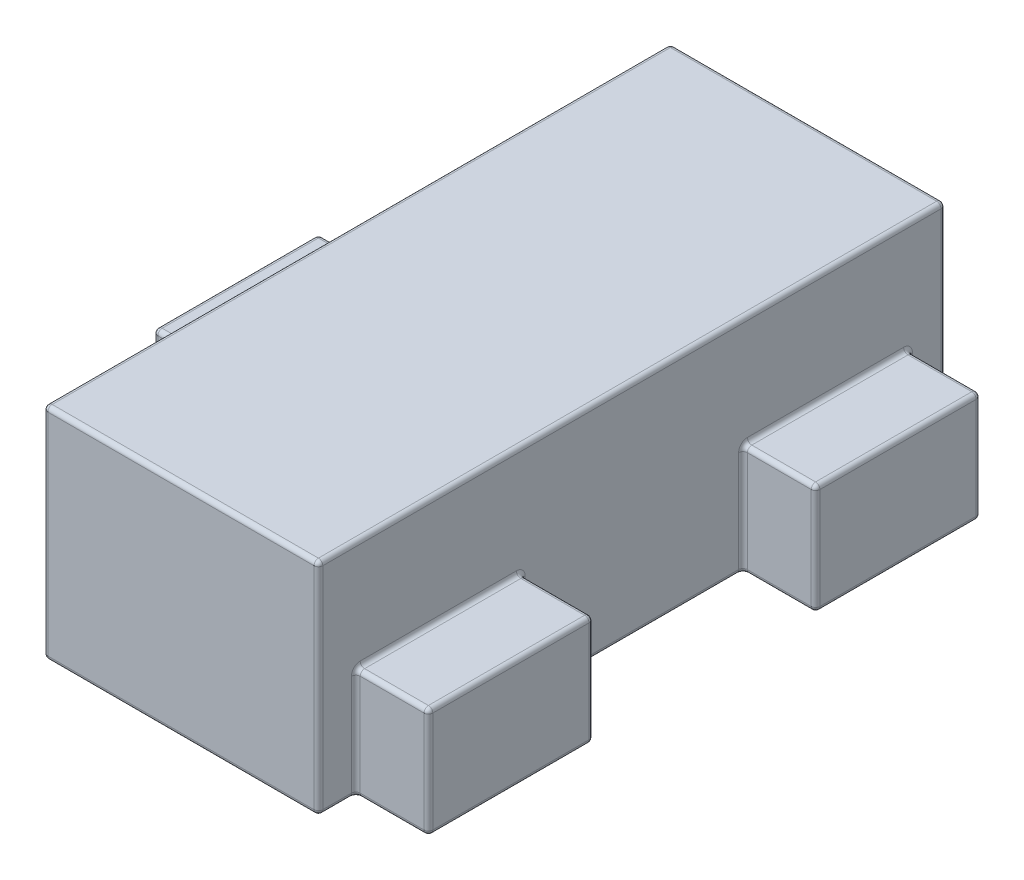
SolidWorks part; units mm, degrees
ref_plane "Front Plane" through (0, 0, 0) normal (0, 0, 1) x (1, 0, 0)
ref_plane "Top Plane" through (0, 0, 0) normal (0, 1, 0) x (1, 0, 0)
ref_plane "Right Plane" through (0, 0, 0) normal (1, 0, 0) x (0, 0, -1)
sketch "Sketch1" plane through (0, 0, 0) normal (0, 1, 0) x (1, 0, 0)
  line L1 (-0.625, 1.425) -> (0.625, 1.425)
  line L2 (-0.625, 1.425) -> (-0.625, -1.425)
  line L3 (-0.625, -1.425) -> (0.625, -1.425)
  line L4 (0.625, 1.425) -> (0.625, -1.425)
  line L5 (-0.625, 1.425) -> (0.625, -1.425) construction
  line L6 (-0.625, -1.425) -> (0.625, 1.425) construction
  point P0 (0, 0)
  dimension "D1" = 1.25
  dimension "D2" = 2.85
extrude "Boss-Extrude1" add sketch "Sketch1" along normal blind 1
sketch "Sketch2" plane through (0, 0, 0) normal (0, 1, 0) x (1, 0, 0)
  line L0 (0, 0) -> (-0.625, 0) construction
  line L1 (-0.625, 1.425) -> (-0.625, -1.425) construction
  line L2 (-0.625, -0.375) -> (-0.625, 0.375)
  line L3 (-0.625, 0.375) -> (-1.175, 0.375)
  line L4 (-1.175, 0.375) -> (-1.175, -0.375)
  line L5 (-1.175, -0.375) -> (-0.625, -0.375)
  line L6 (0.625, -1.425) -> (0.625, 1.425) construction
  line L7 (0.625, 0.505) -> (0.955, 0.505)
  line L8 (0.625, 0.505) -> (0.625, 1.255)
  line L9 (0.625, 1.255) -> (0.955, 1.255)
  line L10 (0.955, 0.505) -> (0.955, 1.255)
  line L11 (0.625, 0.505) -> (0.955, 1.255) construction
  line L12 (0.625, 1.255) -> (0.955, 0.505) construction
  line L13 (0.625, -1.255) -> (0.955, -0.505) construction
  line L14 (0.625, -0.505) -> (0.955, -1.255) construction
  line L15 (0.955, -0.505) -> (0.955, -1.255)
  line L16 (0.625, -1.255) -> (0.955, -1.255)
  line L17 (0.625, -0.505) -> (0.625, -1.255)
  line L18 (0.625, -0.505) -> (0.955, -0.505)
  point P8 (-0.625, 0)
  point P14 (0.79, 0.88)
  point P21 (0.79, -0.88)
  dimension "D1" = 0.75
  dimension "D2" = 0.55
  dimension "D3" = 0.75
  dimension "D4" = 0.33
  dimension "D5" = 0.88
extrude "Boss-Extrude2" add sketch "Sketch2" along normal blind 0.5
fillet "Fillet1" radius 0.02 48 edges at (-0.625, 0.25, 0.375) (-0.625, 0.25, -0.375) (-1.175, 0.25, -0.375) (-1.175, 0.25, 0.375) (0, 1, 1.425) (-0.625, 1, 0) (0.79, 0, 0.505) (0.79, 0, -1.255) (-0.625, 0, -0.9) (-0.9, 0, -0.375) (-1.175, 0, 0) (-0.9, 0, 0.375) (-0.625, 0, 0.9) (0, 0, 1.425) (0.625, 0, 1.34) (0.625, 0.5, 1.425) (0.625, 1, 0) (0.625, 0, -1.34) (0.625, 0.25, -1.255) (0.625, 0, 0) (0.625, 0.25, 0.505) (-0.625, 0.5, 0) (-0.9, 0.5, 0.375) (-1.175, 0.5, 0) (-0.9, 0.5, -0.375) (0.625, 0.5, -1.425) (0, 1, -1.425) (-0.625, 0.5, -1.425) (0, 0, -1.425) (0.79, 0.5, -1.255) (0.625, 0.5, -0.88) (0.79, 0.5, 0.505) (0.625, 0.5, 0.88) (0.625, 0.25, -0.505) (0.79, 0.5, -0.505) (0.79, 0, -0.505) (0.955, 0.25, -0.505) (0.955, 0.5, -0.88) (0.955, 0.25, -1.255) (0.955, 0, -0.88) (0.625, 0.25, 1.255) (0.79, 0.5, 1.255) (0.79, 0, 1.255) (0.955, 0.25, 1.255) (0.955, 0.5, 0.88) (0.955, 0.25, 0.505) (0.955, 0, 0.88) (-0.625, 0.5, 1.425)
sketch "Sketch3" plane through (0, 0, 0) normal (0, -1, 0) x (1, 0, 0)
  line L0 (0.645, 1.235) -> (0.645, 0.525)
  line L1 (0.645, -0.525) -> (0.645, -1.235)
  line L2 (-0.645, 0.355) -> (-0.645, -0.355)
split line "Split Line1"
